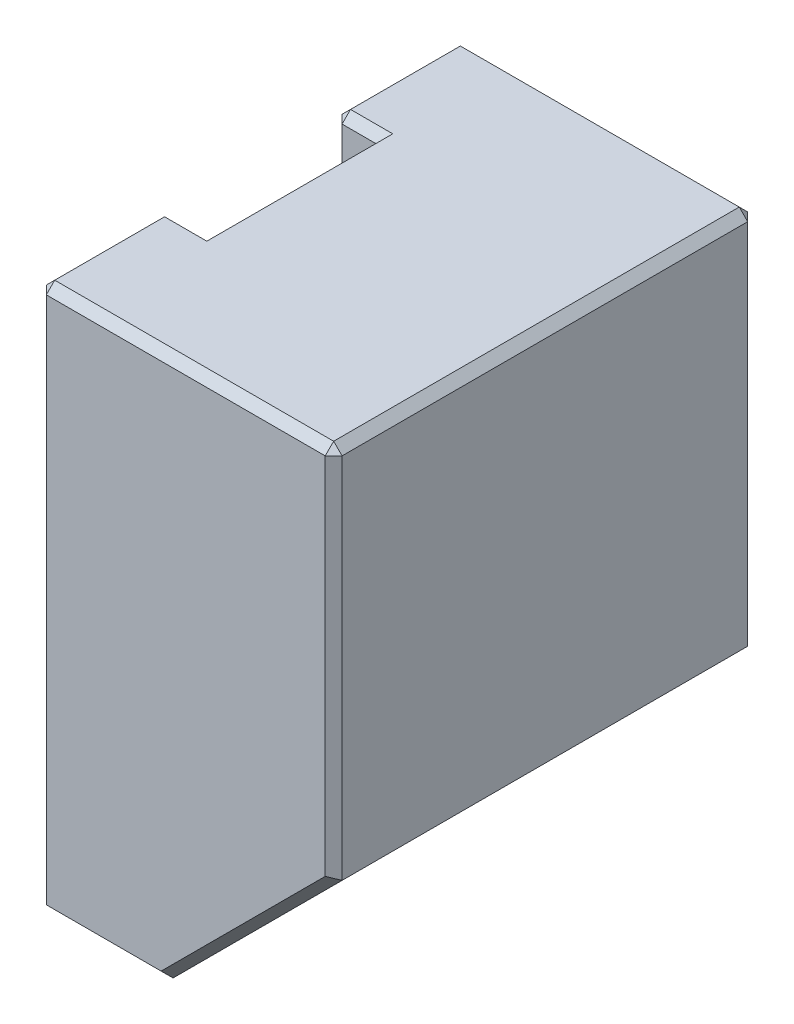
SolidWorks part; units mm, degrees
material "K110"
ref_plane "Front Plane" through (0, 0, 0) normal (0, 0, 1) x (1, 0, 0)
ref_plane "Top Plane" through (0, 0, 0) normal (0, 1, 0) x (1, 0, 0)
ref_plane "Right Plane" through (0, 0, 0) normal (1, 0, 0) x (0, 0, -1)
sketch "Sketch1" plane through (0, 0, 0) normal (0, 1, 0) x (1, 0, 0)
  line L1 (-17.5, -24.995) -> (17.5, -24.995)
  line L2 (-17.5, -24.995) -> (-17.5, 24.995)
  line L3 (-17.5, 24.995) -> (17.5, 24.995)
  line L4 (17.5, -24.995) -> (17.5, 24.995)
  line L5 (-17.5, -24.995) -> (17.5, 24.995) construction
  line L6 (-17.5, 24.995) -> (17.5, -24.995) construction
  point P0 (0, 0)
  dimension "D1" = 49.99
  dimension "D2" = 35
extrude "Boss-Extrude1" add sketch "Sketch1" against normal blind 64.5
sketch "Sketch2" plane through (0, 0, 24.995) normal (0, 0, 1) x (1, 0, 0)
  line L0 (-2.5, -64.5) -> (17.5, -44.5)
  line L1 (-17.5, -64.5) -> (17.5, -64.5) construction
  line L2 (17.5, -64.5) -> (17.5, 0) construction
  line L3 (17.5, -44.5) -> (17.5, -64.5)
  line L4 (17.5, -64.5) -> (-2.5, -64.5)
  dimension "D1" = 20
  dimension "D2" = 45
extrude "Cut-Extrude1" cut sketch "Sketch2" against normal up to next
sketch "Sketch3" plane through (-17.5, 0, 0) normal (-1, 0, 0) x (0, 0, 1)
  line L0 (-24.995, -64.5) -> (24.995, -64.5) construction
  line L1 (-7, -64.5) -> (7, -64.5)
  line L2 (-7, -64.5) -> (-7, -44.5)
  line L3 (-7, -44.5) -> (7, -44.5)
  line L4 (7, -64.5) -> (7, -44.5)
  line L5 (-24.995, -44.5) -> (24.995, -44.5) construction
  point P8 (0, -44.5)
  dimension "D1" = 14
  dimension "D2" = 20
extrude "Cut-Extrude2" cut sketch "Sketch3" against normal up to next
fillet "Fillet1" 2 edges at (0, -44.5, -7) (0, -44.5, 7) type full round first side face at (-5, -54.5, -7) second side face at (-5, -54.5, 7) middle face at (0, -44.5, 0)
sketch "Sketch4" plane through (0, 0, 0) normal (0, 1, 0) x (1, 0, 0)
  line L0 (-17.5, 0) -> (17.5, 0) construction
  line L1 (-17.5, 24.995) -> (-17.5, -24.995) construction
  line L2 (17.5, -24.995) -> (17.5, 24.995) construction
  line L4 (-17.5, -10) -> (-12.5, -10)
  line L5 (-17.5, -10) -> (-17.5, 10)
  line L6 (-17.5, 10) -> (-12.5, 10)
  line L7 (-12.5, -10) -> (-12.5, 10)
  dimension "D1" = 5
  dimension "D2" = 20
extrude "Cut-Extrude3" cut sketch "Sketch4" against normal blind 43
sketch "Sketch5" plane through (-17.5, 0, 0) normal (-1, 0, 0) x (0, 0, 1)
  line L0 (-10, -43) -> (-10, 0) construction
  line L1 (-15, -43) -> (15, -43)
  line L2 (-15, -43) -> (-15, -38)
  line L3 (-15, -38) -> (15, -38)
  line L4 (15, -43) -> (15, -38)
  line L5 (-10, -43) -> (10, -43) construction
  line L6 (10, -43) -> (10, 0) construction
  dimension "D1" = 5
  dimension "D2" = 5
  dimension "D3" = 5
extrude "Cut-Extrude4" cut sketch "Sketch5" against normal up to surface (5 mm away) up to face at (-12.5, -21.5, 0)
fillet "Fillet5" 2 edges at (-15, -43, -15) (-15, -38, -15) type full round first side face at (-15, -43, 0) second side face at (-15, -38, -12.5) middle face at (-15, -40.5, -15)
fillet "Fillet6" 2 edges at (-15, -43, 15) (-15, -38, 15) type full round first side face at (-15, -43, 1.25) second side face at (-15, -38, 12.5) middle face at (-15, -40.5, 15)
chamfer "Chamfer1" distance 1 angle 45 28 edges at (-17.5, -38, 11.25) (-17.5, -19, 10) (-17.5, -64.5, 15.9975) (-17.5, -58, 7) (-17.5, -44.5, 0) (-17.5, -58, -7) (-17.5, -64.5, -15.9975) (-17.5, -40.5, 15) (-17.5, -43, 0) (-17.5, -40.5, -15) (-17.5, -38, -11.25) (-17.5, -19, -10) (17.5, 0, 0) (17.5, -22.25, -24.995) (0, 0, -24.995) (7.5, -54.5, -24.995) (-10, -64.5, -24.995) (-17.5, -32.25, -24.995) (-17.5, 0, -17.4975) (-15, 0, -10) (-12.5, 0, 0) (-15, 0, 10) (-17.5, 0, 17.4975) (-10, -64.5, 24.995) (-17.5, -32.25, 24.995) (0, 0, 24.995) (17.5, -22.25, 24.995) (7.5, -54.5, 24.995)
sketch "Sketch6" plane through (0, 0, 24.995) normal (0, 0, 1) x (1, 0, 0)
  line L0 (-16.5, 0) -> (16.5, 0) construction
  line L1 (-17.5, -63.5) -> (-17.5, -1) construction
  circle A0 centre (-10, -15) radius 2.5
  dimension "D1" = 5
  dimension "D2" = 15
  dimension "D3" = 7.5
extrude "Cut-Extrude5" [suppressed] cut sketch "Sketch6" against normal blind 3
pattern_linear "LPattern1" [suppressed] count 3 spacing 10 count 5 spacing 10 of bodies 106
sketch "Sketch9" plane through (17.5, 0, 0) normal (1, 0, 0) x (0, 0, -1)
  line L0 (-24.995, -44.0858) -> (-24.995, -1) construction
  line L1 (-23.995, 0) -> (23.995, 0) construction
  circle A0 centre (-18.745, -15) radius 2.5
  dimension "D1" = 5
  dimension "D2" = 6.25
  dimension "D3" = 15
extrude "Cut-Extrude20" [suppressed] cut sketch "Sketch9" against normal blind 3
pattern_linear "LPattern2" [suppressed] count 4 spacing 7.5 count 6 spacing 7.5 of bodies 110
sketch "Sketch10" plane through (-17.5, 0, 0) normal (-1, 0, 0) x (0, 0, 1)
  line L0 (-11, -1) -> (-23.995, -1) construction
  line L2 (-23.995, 0) -> (-11, 0) construction
  circle A0 centre (-17.4975, -15) radius 2.5
  point P7 (-17.4975, -1)
  dimension "D1" = 5
  dimension "D2" = 15
extrude "Cut-Extrude21" [suppressed] cut sketch "Sketch10" against normal blind 3
pattern_linear "LPattern3" [suppressed] count 7 spacing 7.5 count 2 spacing 35 of bodies 112
sketch "Sketch11" plane through (31, -31, 0) normal (0.7071, -0.7071, 0) x (0, 0, -1)
  line L0 (-24.995, -46.9619) -> (-24.995, -19.5061) construction
  line L2 (0, -19.0919) -> (-23.995, -19.0919) construction
  circle A0 centre (-18.745, -26.5919) radius 2.5
  dimension "D1" = 6.25
  dimension "D2" = 5
  dimension "D5" = 7.5
extrude "Cut-Extrude23" [suppressed] cut sketch "Sketch11" against normal blind 3
pattern_linear "LPattern5" [suppressed] count 6 spacing 7.5 count 3 spacing 7.5 of bodies 115
sketch "Sketch18" [suppressed] plane through (0, 0, -25) normal (0, 0, -1) x (-1, 0, 0)
  circle A0 centre (10, -15) radius 2.5
extrude "Cut-Extrude25" [suppressed] cut sketch "Sketch18" against normal blind 3
pattern_linear "LPattern7" [suppressed] count 3 spacing 10 count 5 spacing 10 of bodies 121
ref_plane "Plane1" through (31, -31, 0) normal (0.7071, -0.7071, 0) x (-0.7071, -0.7071, 0)
sketch "Sketch19" plane through (31, -31, 0) normal (0.7071, -0.7071, 0) x (0, 0, -1)
  line L0 (0, -19.0919) -> (0, -47.3762)
  line L3 (23.995, -33.234) -> (-24.995, -33.234)
  line L4 (23.995, -47.3762) -> (23.995, -19.0919) construction
  line L5 (-24.995, -46.9619) -> (-24.995, -19.5061) construction
  line L6 (-7, -47.3762) -> (-23.995, -47.3762) construction
sketch "Sketch20" plane through (0, 0, 0) normal (0, 0, 1) x (1, 0, 0)
  line L0 (7.5, -54.5) -> (0.4289, -47.4289)
  line L1 (17.5, -44.5) -> (-2.5, -64.5) construction
  line L2 (-2.9142, -63.5) -> (16.5, -44.0858) construction
  dimension "D1" = 10
